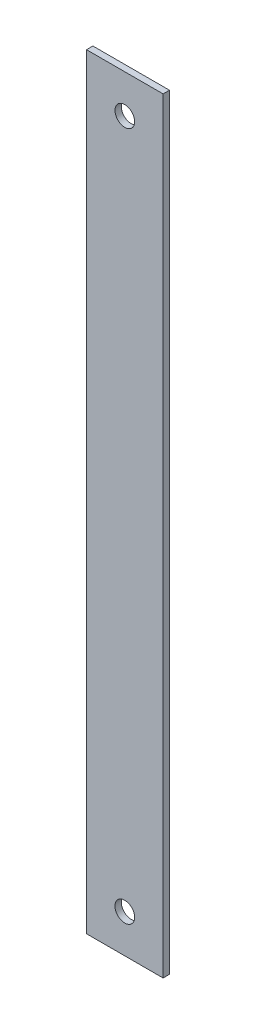
SolidWorks part; units mm, degrees
material "Plain Carbon Steel"
ref_plane "Front Plane" through (0, 0, 0) normal (0, 0, 1) x (1, 0, 0)
ref_plane "Top Plane" through (0, 0, 0) normal (0, 1, 0) x (1, 0, 0)
ref_plane "Right Plane" through (0, 0, 0) normal (1, 0, 0) x (0, 0, -1)
sketch "Sketch1" plane through (0, 0, 0) normal (0, 0, 1) x (1, 0, 0)
  line L1 (0, 0) -> (38.1, 0)
  line L2 (0, 0) -> (0, 381)
  line L3 (0, 381) -> (38.1, 381)
  line L4 (38.1, 0) -> (38.1, 381)
  dimension "D1" = 38.1
  dimension "D2" = 381
extrude "Boss-Extrude1" add sketch "Sketch1" along normal blind 3.175
hole_wizard "W (0.386) Diameter Hole1" positions "Sketch3" profile "Sketch2" hole size "W" standard "ANSI Inch" end condition through all
sketch "Sketch3" plane through (0, 0, 3.175) normal (0, 0, 1) x (1, 0, 0)
  line L0 (19.05, 0) -> (19.05, 19.05) construction
  line L1 (0, 0) -> (38.1, 0) construction
  line L2 (19.05, 19.05) -> (19.05, 361.95) construction
  line L3 (19.05, 361.95) -> (19.05, 381) construction
  line L4 (38.1, 381) -> (0, 381) construction
  point P0 (19.05, 361.95)
  point P2 (19.05, 19.05)
  dimension "D1" = 19.05
sketch "Sketch2" plane through (19.05, 361.95, 3.175) normal (1, 0, 0) x (0, -1, 0)
  line L0 (0, 0) -> (0, 3.175)
  line L1 (0, 3.175) -> (4.9022, 3.175)
  line L2 (4.9022, 3.175) -> (4.9022, 0)
  line L5 (4.9022, 0) -> (0, 0)
  line L11 (0, -6.35) -> (0, 107.95) construction
  dimension "Thru Hole Dia." = 9.8044
  dimension "Thru Hole Depth" = 3.175
